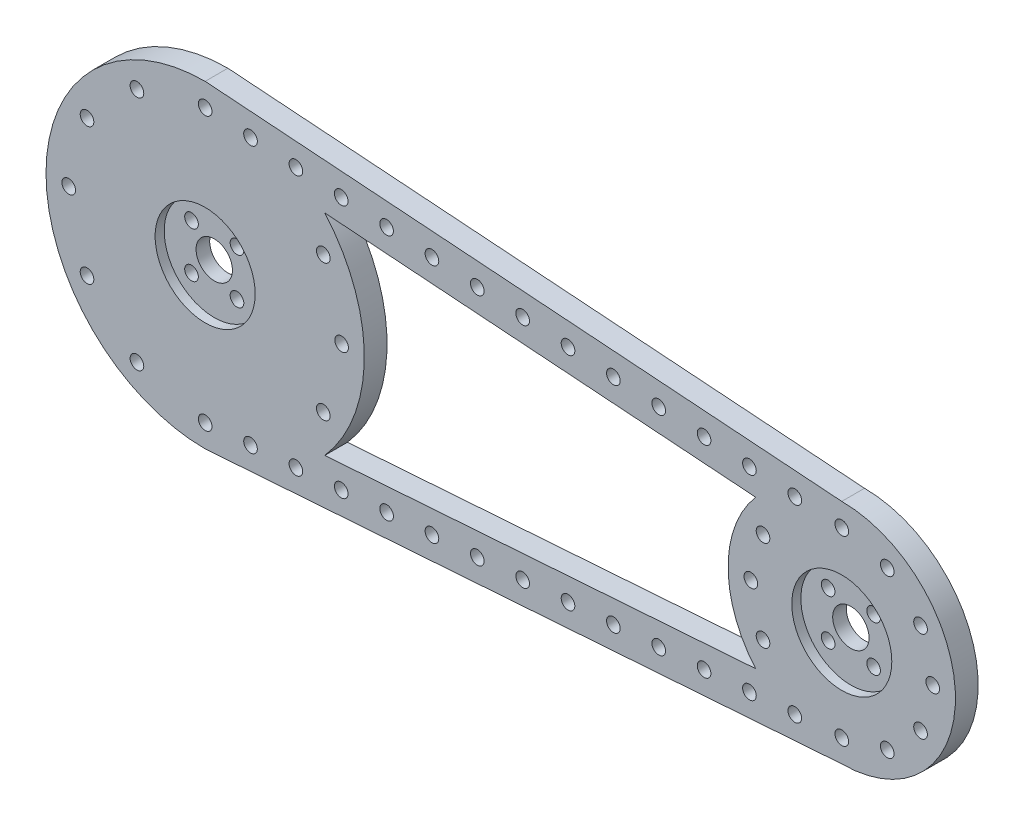
SolidWorks part; units mm, degrees
ref_plane "前视基准面" through (0, 0, 0) normal (0, 0, 1) x (1, 0, 0)
ref_plane "上视基准面" through (0, 0, 0) normal (0, 1, 0) x (1, 0, 0)
ref_plane "右视基准面" through (0, 0, 0) normal (1, 0, 0) x (0, 0, -1)
other "Configuration Table"
sketch "草图1" plane through (0, 0, 0) normal (0, 0, 1) x (1, 0, 0)
  line L0 (0, 0) -> (140, 0)
  line L1 (0, 35) -> (140, 25)
  line L2 (0, -35) -> (140, -25)
  circle A0 centre (0, 0) radius 35
  circle A1 centre (140, 0) radius 25
  dimension "D1" = 70
  dimension "D3" = 50
  dimension "D2" = 140
extrude "凸台-拉伸3" add sketch "草图1" along normal blind 5 contours A0 L1 L2 | A1 L0 A0 L2 | A1 L1 A0 L0 | A1 region at (72.7482, 16.0498, 0) region at (-0.0004, 0, 0) region at (72.7482, -16.0498, 0) region at (122.8223, 17.1777, 0)
sketch "草图4" plane through (0, 0, 5) normal (0, 0, 1) x (1, 0, 0)
  line L1 (-5, -5) -> (5, -5)
  line L2 (-5, -5) -> (-5, 5)
  line L3 (-5, 5) -> (5, 5)
  line L4 (5, -5) -> (5, 5)
  line L5 (-5, -5) -> (5, 5) construction
  line L6 (-5, 5) -> (5, -5) construction
  line L7 (135, -5) -> (145, -5)
  line L8 (135, -5) -> (135, 5)
  line L9 (135, 5) -> (145, 5)
  line L10 (145, -5) -> (145, 5)
  line L11 (135, -5) -> (145, 5) construction
  line L12 (135, 5) -> (145, -5) construction
  circle A0 centre (0, 0) radius 4
  circle A1 centre (-5, 5) radius 1.5
  circle A2 centre (5, 5) radius 1.5
  circle A3 centre (5, -5) radius 1.5
  circle A4 centre (-5, -5) radius 1.5
  circle A5 centre (140, 0) radius 4
  circle A6 centre (135, 5) radius 1.5
  circle A7 centre (145, 5) radius 1.5
  circle A8 centre (145, -5) radius 1.5
  circle A9 centre (135, -5) radius 1.5
  dimension "D1" = 8
  dimension "D4" = 3
  dimension "D6" = 8
  dimension "D9" = 3
  dimension "D2" = 10
  dimension "D3" = 10
  dimension "D7" = 10
  dimension "D8" = 10
  dimension "D5" = 4
  dimension "D10" = 4
extrude "切除-拉伸3" cut sketch "草图4" against normal blind 5 contours A5 | A0 | L2 A4 L1 | L1 A4 L2 | A6 | A9 | A8 | A7 | A1 | A2 | A3 region at (-4.3634, -4.3634, 5) region at (-5.2122, -5.2122, 5) region at (0, 0, 5) region at (140, 0, 5)
sketch "草图5" plane through (0, 0, 5) normal (0, 0, 1) x (1, 0, 0)
  circle A0 centre (0, 0) radius 11
  circle A1 centre (140, 0) radius 11
  dimension "D1" = 22
  dimension "D2" = 22
extrude "切除-拉伸4" cut sketch "草图5" against normal blind 2
sketch "草图6" plane through (0, 0, 5) normal (0, 0, 1) x (1, 0, 0)
  circle A0 centre (0, 0) radius 30
  circle A1 centre (0, 30) radius 1.5
  circle A2 centre (15, 25.9808) radius 1.5
  circle A3 centre (25.9808, 15) radius 1.5
  circle A4 centre (30, 0) radius 1.5
  circle A5 centre (25.9808, -15) radius 1.5
  circle A6 centre (15, -25.9808) radius 1.5
  circle A7 centre (0, -30) radius 1.5
  circle A8 centre (-15, -25.9808) radius 1.5
  circle A9 centre (-25.9808, -15) radius 1.5
  circle A10 centre (-30, 0) radius 1.5
  circle A11 centre (-25.9808, 15) radius 1.5
  circle A12 centre (-15, 25.9808) radius 1.5
  circle A13 centre (140, 0) radius 20
  circle A14 centre (140, 20) radius 1.5
  circle A15 centre (150, 17.3205) radius 1.5
  circle A16 centre (157.3205, 10) radius 1.5
  circle A17 centre (160, 0) radius 1.5
  circle A18 centre (157.3205, -10) radius 1.5
  circle A19 centre (150, -17.3205) radius 1.5
  circle A20 centre (140, -20) radius 1.5
  circle A21 centre (130, -17.3205) radius 1.5
  circle A22 centre (122.6795, -10) radius 1.5
  circle A23 centre (120, 0) radius 1.5
  circle A24 centre (122.6795, 10) radius 1.5
  circle A25 centre (130, 17.3205) radius 1.5
  point P29 (0, 0)
  dimension "D1" = 60
  dimension "D2" = 3
  dimension "D4" = 40
  dimension "D5" = 3
  dimension "D3" = 12
  dimension "D6" = 12
extrude "切除-拉伸6" cut sketch "草图6" against normal through all contours A0 A12 | A11 | A12 | A1 | A2 | A3 | A4 | A5 | A6 | A7 | A8 | A9 | A10 | A25 | A14 | A15 | A16 | A17 | A18 | A19 | A20 | A21 | A22 | A23 | A24 region at (-14.6783, 25.4236, 5)
sketch "草图8" plane through (0, 0, 5) normal (0, 0, 1) x (1, 0, 0)
  line L4 (-0.1715, -29.9995) -> (139.8316, -19.9993)
  line L5 (139.8316, 19.9993) -> (-0.1715, 29.9995)
  line L6 (-0.1715, -29.9995) -> (139.8316, -19.9993)
  line L7 (139.8316, 19.9993) -> (-0.1715, 29.9995)
  line L8 (-0.7125, 25.0254) -> (139.2875, 15.0254)
  line L9 (-0.7125, 25.0254) -> (139.2875, 15.0254)
  line L11 (-0.7125, -25.0254) -> (139.2875, -15.0254)
  line L12 (-0.7125, -25.0254) -> (139.2875, -15.0254)
  circle A3 centre (0, 30) radius 1.5
  arc A4 (139.8316, -19.9993) -> (139.8316, 19.9993) centre (140, 0) ccw
  arc A5 (-0.1715, 29.9995) -> (-0.1715, -29.9995) centre (0, 0) ccw
  arc A6 (139.8316, -19.9993) -> (139.8316, 19.9993) centre (140, 0) ccw
  arc A7 (-0.1715, 29.9995) -> (-0.1715, -29.9995) centre (0, 0) ccw
  circle A8 centre (9.9746, 29.2875) radius 1.5
  circle A9 centre (19.9492, 28.5751) radius 1.5
  circle A10 centre (29.9238, 27.8626) radius 1.5
  circle A11 centre (39.8983, 27.1501) radius 1.5
  circle A12 centre (49.8729, 26.4376) radius 1.5
  circle A13 centre (59.8475, 25.7252) radius 1.5
  circle A14 centre (69.8221, 25.0127) radius 1.5
  circle A15 centre (79.7967, 24.3002) radius 1.5
  circle A16 centre (89.7713, 23.5878) radius 1.5
  circle A17 centre (99.7459, 22.8753) radius 1.5
  circle A18 centre (109.7205, 22.1628) radius 1.5
  circle A19 centre (119.695, 21.4504) radius 1.5
  circle A20 centre (129.6696, 20.7379) radius 1.5
  circle A21 centre (0, -30) radius 1.5
  circle A22 centre (9.9746, -29.2875) radius 1.5
  circle A23 centre (19.9492, -28.5751) radius 1.5
  circle A24 centre (29.9238, -27.8626) radius 1.5
  circle A25 centre (39.8983, -27.1501) radius 1.5
  circle A26 centre (49.8729, -26.4376) radius 1.5
  circle A27 centre (59.8475, -25.7252) radius 1.5
  circle A28 centre (69.8221, -25.0127) radius 1.5
  circle A29 centre (79.7967, -24.3002) radius 1.5
  circle A30 centre (89.7713, -23.5878) radius 1.5
  circle A31 centre (99.7459, -22.8753) radius 1.5
  circle A32 centre (109.7205, -22.1628) radius 1.5
  circle A33 centre (119.695, -21.4504) radius 1.5
  circle A34 centre (129.6696, -20.7379) radius 1.5
  circle A35 centre (0, 0) radius 35
  circle A36 centre (140, 0) radius 25
  dimension "D2" = 14
  dimension "D1" = 5
  dimension "D4" = 10
  dimension "D5" = 10
  dimension "D3" = 14
extrude "切除-拉伸8" cut sketch "草图8" against normal through all contours A36 L9 A35 L12 | L6 A25 | L6 A25 | A8 | A9 | A10 | A11 | A12 | A13 | A14 | A16 | A15 | A17 | A18 | A19 | A20 | A34 | A33 | A32 | A31 | A30 | A29 | A28 | A27 | A26 | A24 | A23 | A22 region at (72.4357, 0, 5) region at (39.8525, -26.5083, 5) region at (39.9432, -27.7783, 5)
sketch "草图9" plane through (0, 0, 5) normal (0, 0, 1) x (1, 0, 0)
  circle A0 centre (15, 25.9808) radius 1.5
  circle A1 centre (15, -25.9808) radius 1.5
extrude "凸台-拉伸4" add sketch "草图9" against normal blind 5
sketch "草图10" plane through (0, 0, 5) normal (0, 0, 1) x (1, 0, 0)
  circle A0 centre (130, -17.3205) radius 1.5
  circle A1 centre (130, 17.3205) radius 1.5
extrude "凸台-拉伸6" add sketch "草图10" against normal blind 5
